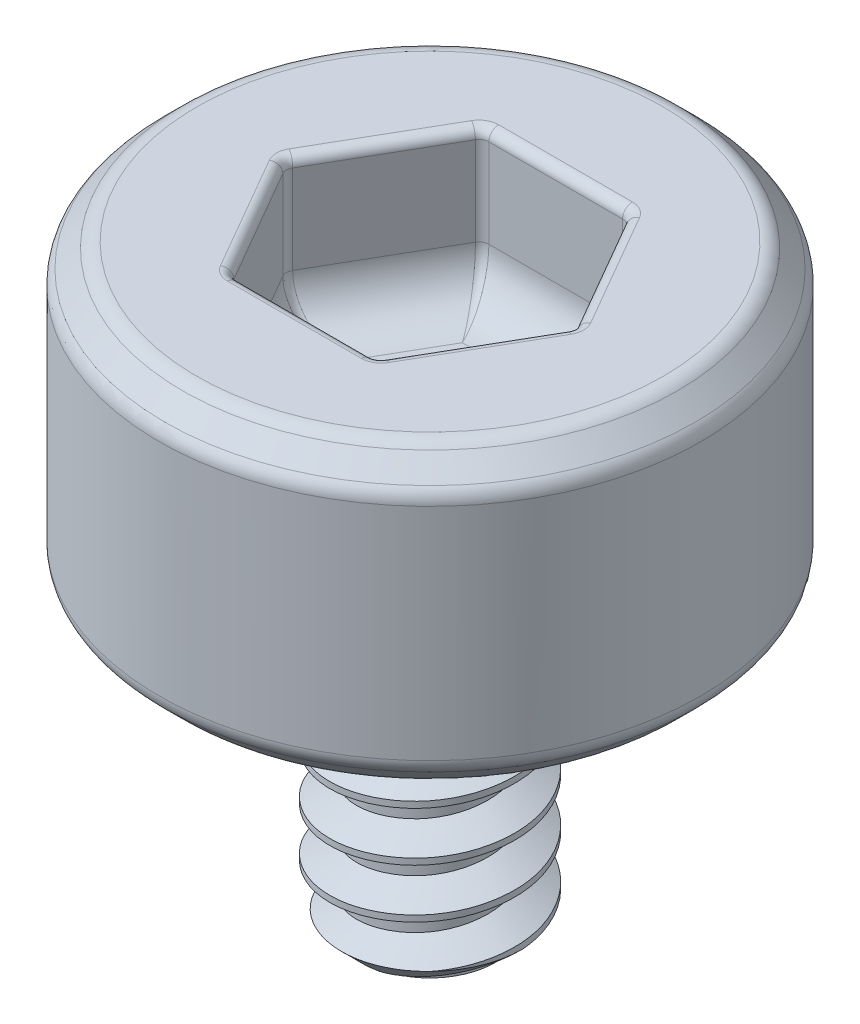
SolidWorks part; units mm, degrees
ref_plane "Front" through (0, 0, 0) normal (0, 0, 1) x (1, 0, 0)
ref_plane "Top" through (0, 0, 0) normal (0, 1, 0) x (1, 0, 0)
ref_plane "Right" through (0, 0, 0) normal (1, 0, 0) x (0, 0, -1)
sketch "Sketch8" plane through (0, 0, 0) normal (0, 0, 1) x (1, 0, 0)
  line L1 (0, 0) -> (0.9375, 0)
  line L2 (0, 0) -> (0, -6)
  line L3 (0, -6) -> (0.9375, -6)
  line L4 (0.9375, 0) -> (0.9375, -6)
  dimension "D1" = 6
revolve "Revolve1" add sketch "Sketch8" angle 360 about L2
chamfer "Chamfer1" distance 0.25 angle 45 1 edges at (-0.9375, -6, 0)
sketch "Sketch9" plane through (0, 0, 0) normal (0, 1, 0) x (1, 0, 0)
  circle A0 centre (0, 0) radius 1.5
thread "Thread2" pitch 0.5 method cut profile "Thread Profile2" start angle 0, offset 0, length 10, pitch 0.5, diameter 1.875
ref_plane "Plane2" through (-0.9375, 0, 0) normal (0, 0, -1) x (1, 0, 0)
sketch "Thread Profile2" plane through (-0.9375, 0, 0) normal (0, 0, -1) x (1, 0, 0)
  line L0 (0, 0) -> (0, 0.5) construction
  line L11 (0, 0.4375) -> (0, 0)
  line L12 (0, 0) -> (0.2706, 0.1563)
  line L13 (0.2706, 0.1563) -> (0.2706, 0.2813)
  line L15 (0.2706, 0.2813) -> (0, 0.4375)
  line L17 (0.2706, 0.2188) -> (0, 0.2188) construction
  point P3 (0, 0)
  dimension "Pitch" = 0.5
  dimension "Profile_Angle" = 60
  dimension "Profile_Land" = 0.125
  dimension "Profile_Height" = 0.2706
sketch "Sketch13" plane through (0, 0, 0) normal (0, 0, 1) x (1, 0, 0)
  line L0 (0, 0) -> (2.75, 0)
  line L1 (0, 0) -> (0, -3)
  line L2 (0, -3) -> (2.75, -3)
  line L3 (2.75, -3) -> (2.75, 0)
revolve "Revolve2" add sketch "Sketch13" angle 360 about L1
chamfer "Chamfer2" distance 0.3 angle 45 2 edges at (-2.75, 0, 0) (-2.75, -3, 0)
fillet "Fillet1" radius 0.2 4 edges at (-2.45, -3, 0) (-2.75, -2.7, 0) (2.75, -0.3, 0) (2.45, 0, 0)
sketch "Sketch14" plane through (0, 0, 0) normal (0, 1, 0) x (1, 0, 0)
  line L1 (1.4722, 0) -> (0.7361, 1.275)
  line L2 (0.7361, 1.275) -> (-0.7361, 1.275)
  line L3 (-0.7361, 1.275) -> (-1.4722, 0)
  line L4 (-1.4722, 0) -> (-0.7361, -1.275)
  line L5 (-0.7361, -1.275) -> (0.7361, -1.275)
  line L6 (0.7361, -1.275) -> (1.4722, 0)
  circle A0 centre (0, 0) radius 1.275 construction
extrude "Cut-Extrude1" cut sketch "Sketch14" against normal blind 1.5
fillet "Fillet2" radius 0.5 6 edges at (0, -1.5, 1.275) (-1.1042, -1.5, 0.6375) (-1.1042, -1.5, -0.6375) (0, -1.5, -1.275) (1.1042, -1.5, -0.6375) (1.1042, -1.5, 0.6375)
fillet "Fillet3" radius 0.1 18 edges at (1.1042, 0, 0.6375) (0, 0, -1.275) (-1.1042, 0, 0.6375) (1.3031, -1.3536, 0) (0.6516, -1.3536, -1.1286) (-0.6516, -1.3536, 1.1286) (0.6516, -1.3536, 1.1286) (-0.6516, -1.3536, -1.1286) (-1.3031, -1.3536, 0) (1.1042, 0, -0.6375) (1.4722, -0.5, 0) (0.7361, -0.5, -1.275) (0, 0, 1.275) (-0.7361, -0.5, 1.275) (0.7361, -0.5, 1.275) (-1.1042, 0, -0.6375) (-0.7361, -0.5, -1.275) (-1.4722, -0.5, 0)
ref_plane "Plane3" through (-2.75, 0, 0) normal (-1, 0, 0) x (0, 0, 1)
